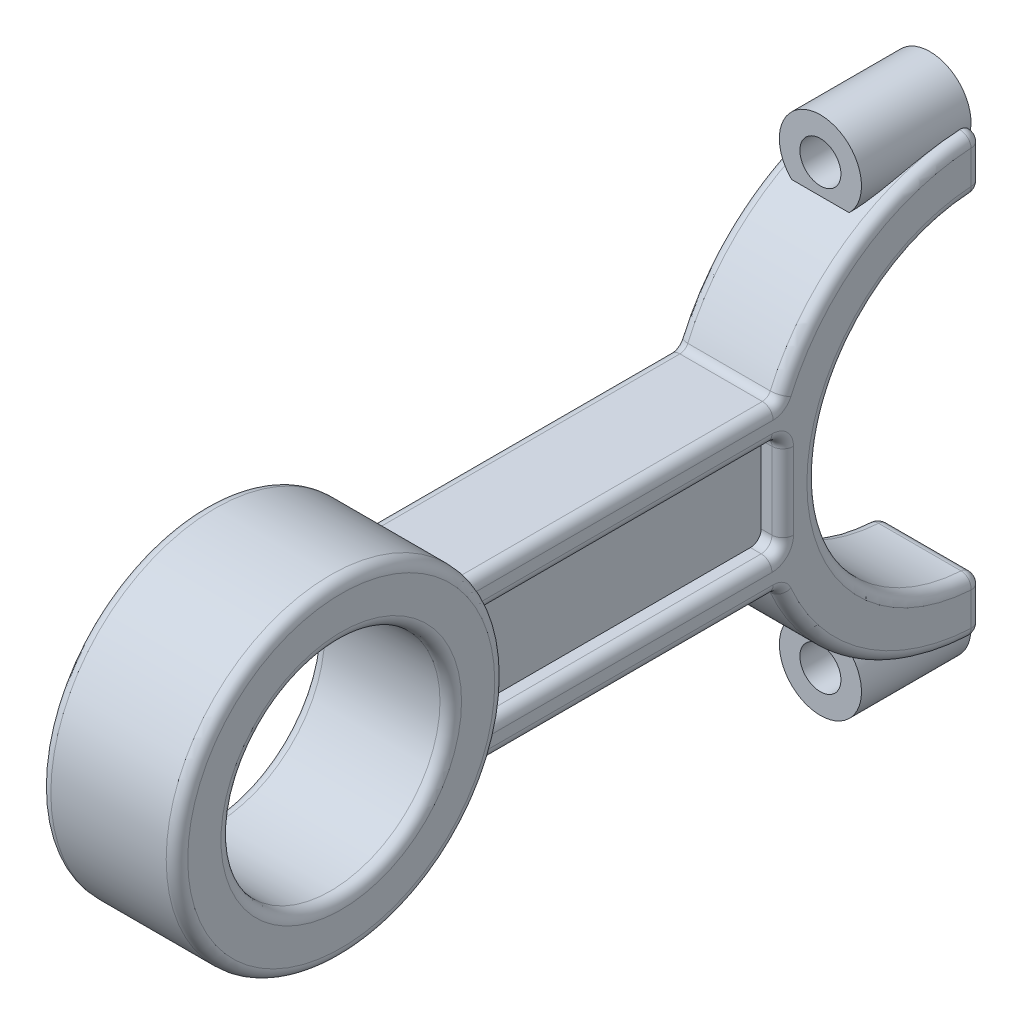
SolidWorks part; units mm, degrees
note: The reader was unsure of these and kept them because the rebuilt part matched: shared geometry of "Sketch1<3>", "Sketch1<5>", "Sketch2<3>".
ref_plane "Front Plane" through (0, 0, 0) normal (0, 0, 1) x (1, 0, 0)
ref_plane "Top Plane" through (0, 0, 0) normal (0, 1, 0) x (1, 0, 0)
ref_plane "Right Plane" through (0, 0, 0) normal (1, 0, 0) x (0, 0, -1)
sketch "Sketch1" plane through (0, 0, 0) normal (1, 0, 0) x (0, 0, -1)
  line L0 (-110.5144, 0) -> (184.5495, 0) construction
  line L1 (0, 38.3833) -> (0, -42.5706) construction
  line L2 (76.2, 69.2738) -> (76.2, -70.0259) construction
  line L3 (-76.2, 66.5596) -> (-76.2, -66.5596) construction
  line L4 (76.2, -38.1) -> (76.2, -50.8)
  line L5 (-43.1987, 19.04) -> (29.1031, 19.04)
  line L7 (-43.1987, -19.04) -> (29.1031, -19.04)
  line L8 (30, 11.42) -> (30, -11.42)
  line L9 (76.2, 38.1) -> (76.2, 50.8)
  line L11 (-39.8518, 11.42) -> (30, 11.42)
  line L13 (-39.8518, -11.42) -> (30, -11.42)
  line L14 (30, 11.42) -> (30, -11.42)
  circle A0 centre (-76.2, 0) radius 25.4
  circle A1 centre (-76.2, 0) radius 38.1
  arc A2 (76.2, 38.1) -> (76.2, -38.1) centre (76.2, 0) ccw
  arc A3 (76.2, 50.8) -> (29.1031, 19.04) centre (76.2, 0) ccw
  arc A5 (29.1031, -19.04) -> (76.2, -50.8) centre (76.2, 0) ccw
  point P21 (-43.2, 19.0423)
  point P22 (-43.1987, -19.04)
  point P24 (29.1031, -19.04)
  point P26 (28.5933, -19.04)
  point P27 (30, -11.42)
  point P29 (0, 0)
  point P30 (30, 19.04)
  point P32 (28.6961, 19.04)
  point P33 (76.2, -51.2402)
  point P34 (30, -11.42)
  dimension "D1" = 50.8
  dimension "D2" = 76.2
  dimension "D3" = 76.2
  dimension "D4" = 101.6
  dimension "D10" = 50.8
  dimension "D5" = 152.4
  dimension "D6" = 76.2
  dimension "D7" = 38.08
  dimension "D8" = 22.84
  dimension "D9" = 30
extrude "Boss-Extrude1" add sketch "Sketch1" along normal mid plane 31.75 contours A1 A0
extrude "Boss-Extrude2" add sketch "Sketch1<3>" along normal mid plane 24.13 contours L7 A5 L4 A2 L9 A3 L5 A1 L11 L8 L13
sketch "Sketch1<3>" plane through (0, 0, 0) normal (1, 0, 0) x (0, 0, -1) same geometry as "Sketch1"
extrude "Boss-Extrude3" add sketch "Sketch1<5>" along normal mid plane 14.13 contours A1 L13 L8 L11
sketch "Sketch1<5>" plane through (0, 0, 0) normal (1, 0, 0) x (0, 0, -1) same geometry as "Sketch1"
sketch "Sketch2" plane through (0, 0, -76.2) normal (0, 0, -1) x (-1, 0, 0)
  line L0 (0, 69.6672) -> (0, -99.4818) construction
  line L1 (39.5754, 0) -> (-36.369, 0) construction
  circle A0 centre (0, 50.8) radius 4.76
  circle A1 centre (0, 50.8) radius 9.525
  circle A2 centre (0, -50.8) radius 9.525
  circle A3 centre (0, -50.8) radius 4.76
  point P11 (0, 0)
  line M2 (12.065, 50.8) -> (-12.065, 50.8)
  dimension "D1" = 9.52
  dimension "D2" = 19.05
  dimension "D3" = 101.6
extrude "Boss-Extrude4" add sketch "Sketch2" against normal blind 25.4 contours A3 | A2 A3 | A0 M2 | A0 M2 | A1 A0 M2 | A1 A0 M2
extrude "Cut-Extrude1" cut sketch "Sketch2<3>" against normal blind 25.4 contours A3 | A0 M2 | A0 M2
sketch "Sketch2<3>" plane through (0, 0, -76.2) normal (0, 0, -1) x (-1, 0, 0) same geometry as "Sketch2"
fillet "Fillet1" radius 2 2 edges at (0, -19.04, -29.1031) (0, 19.04, -29.1031)
fillet "Fillet2" radius 2.5 40 edges at (15.875, 0, 38.1) (-12.065, -19.04, 7.7127) (12.065, -44.45, -76.2) (10.795, -50.8, -76.2) (12.065, 0, -38.1) (0, -38.1, -76.2) (-12.065, 44.45, -76.2) (0, 38.1, -76.2) (-12.065, 42.4793, -48.3406) (10.795, 50.8, -76.2) (12.065, 19.04, 7.7127) (-12.065, 11.42, 4.9259) (-12.065, 0, -30) (9.565, 11.42, -30) (12.065, -11.42, 4.9259) (9.565, -11.42, -30) (12.065, -19.04, 7.7127) (12.065, 44.45, -76.2) (12.065, 42.4793, -48.3406) (12.065, 11.42, 4.9259) (12.065, 0, -30) (-12.065, -11.42, 4.9259) (-12.065, 19.04, 7.7127) (-12.065, 0, -38.1) (-12.065, -44.45, -76.2) (-15.875, 0, 38.1) (-9.565, -11.42, -30) (-15.875, 0, 50.8) (-9.565, 11.42, -30) (-10.795, -50.8, -76.2) (9.0943, -47.9682, -59.4759) (-10.795, 50.8, -76.2) (9.0943, 47.9682, -59.4759) (15.875, 0, 50.8) (12.065, -42.4793, -48.3406) (-12.065, -42.4793, -48.3406) (-12.065, -19.3676, -28.87) (12.065, -19.3676, -28.87) (-12.065, 19.3676, -28.87) (12.065, 19.3676, -28.87)
